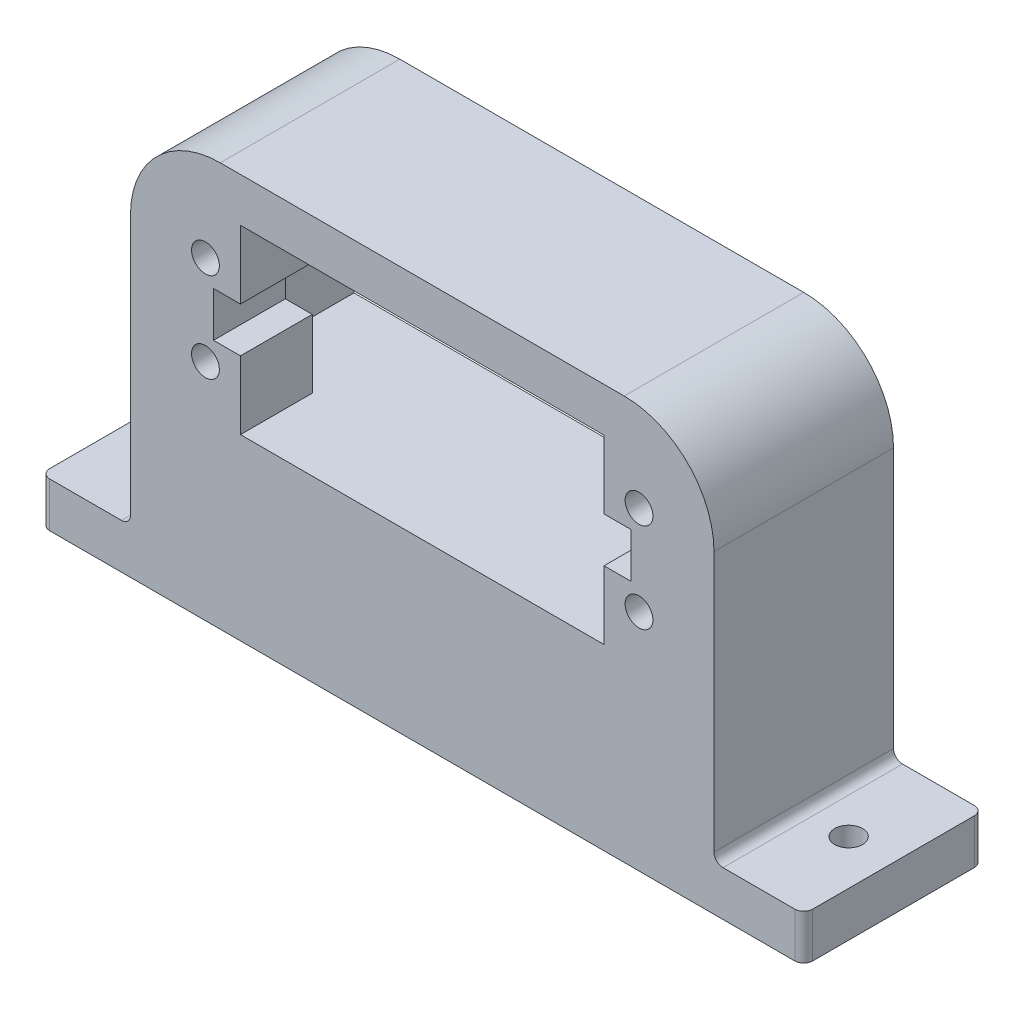
SolidWorks part; units mm, degrees
ref_plane "Front Plane" through (0, 0, 0) normal (0, 0, 1) x (1, 0, 0)
ref_plane "Top Plane" through (0, 0, 0) normal (0, 1, 0) x (1, 0, 0)
ref_plane "Right Plane" through (0, 0, 0) normal (1, 0, 0) x (0, 0, -1)
sketch "Sketch1" plane through (0, 0, 0) normal (0, 0, 1) x (1, 0, 0)
  line L0 (-42.5, 0) -> (42.5, 0)
  line L1 (32.5, 5) -> (32.5, 35)
  line L2 (22.5, 45) -> (-22.5, 45)
  line L3 (-32.5, 35) -> (-32.5, 5)
  line L4 (-42.5, 0) -> (-42.5, 5)
  line L5 (-42.5, 5) -> (-32.5, 5)
  line L7 (42.5, 0) -> (42.5, 5)
  line L8 (42.5, 5) -> (32.5, 5)
  arc A1 (32.5, 35) -> (22.5, 45) centre (22.5, 35) ccw
  arc A2 (-22.5, 45) -> (-32.5, 35) centre (-22.5, 35) ccw
  dimension "D1" = 10
  dimension "D2" = 45
  dimension "D3" = 65
  dimension "D4" = 10
  dimension "D5" = 5
extrude "Boss-Extrude1" add sketch "Sketch1" along normal mid plane 20
sketch "Sketch3" plane through (0, 0, -10) normal (0, 0, -1) x (-1, 0, 0)
  line L0 (-24.15, 25) -> (-24.15, 35) construction
  line L1 (-27.6, 19.9) -> (27.6, 19.9)
  line L2 (-27.6, 19.9) -> (-27.6, 40.1)
  line L3 (-27.6, 40.1) -> (27.6, 40.1)
  line L4 (27.6, 19.9) -> (27.6, 40.1)
  line L5 (-27.6, 19.9) -> (27.6, 40.1) construction
  line L6 (-27.6, 40.1) -> (27.6, 19.9) construction
  line L7 (20.25, 19.9) -> (-20.25, 19.9)
  line L8 (20.25, 19.9) -> (20.25, 40.1)
  line L9 (20.25, 40.1) -> (-20.25, 40.1)
  line L10 (-20.25, 19.9) -> (-20.25, 40.1)
  line L11 (20.25, 19.9) -> (-20.25, 40.1) construction
  line L12 (20.25, 40.1) -> (-20.25, 19.9) construction
  line L13 (24.15, 25) -> (24.15, 35) construction
  line L14 (-24.15, 30) -> (24.15, 30) construction
  line L15 (-20.25, 27.5) -> (-23.25, 27.5)
  line L16 (-23.25, 27.5) -> (-23.25, 32.5)
  line L17 (-23.25, 32.5) -> (-20.25, 32.5)
  line L19 (20.25, 32.5) -> (23.25, 32.5)
  line L20 (23.25, 32.5) -> (23.25, 27.5)
  line L21 (23.25, 27.5) -> (20.25, 27.5)
  circle A0 centre (-24.15, 25) radius 1.55
  circle A1 centre (24.15, 25) radius 1.55
  circle A2 centre (-24.15, 35) radius 1.55
  circle A3 centre (24.15, 35) radius 1.55
  point P0 (0, 30)
  point P7 (0, 30)
  point P22 (0, 30)
  point P27 (-23.25, 30)
  point P28 (-21.75, 32.5)
  point P34 (23.25, 30)
  dimension "D5" = 3.1
  dimension "D1" = 30
  dimension "D2" = 55.2
  dimension "D3" = 20.2
  dimension "D4" = 40.5
  dimension "D6" = 48.3
  dimension "D7" = 10
  dimension "D8" = 5
  dimension "D9" = 3
extrude "Cut-Extrude1" cut sketch "Sketch3" against normal blind 12 contours L8 L1 L4 L3 | L1 L10 L3 L2 region at (24.1719, 30, -10) region at (-24.1719, 30, -10)
extrude "Cut-Extrude3" cut sketch "Sketch3<3>" against normal through all contours L10 L1 L8 L3 | A0 | A3 | L17 L16 L15 L10 | L21 L20 L19 L8 | A2 | A1 region at (0, 30, -10) region at (21.75, 30, -10) region at (-21.75, 30, -10) region at (24.15, 25, -10) region at (-24.15, 35, -10)
sketch "Sketch3<3>" plane through (0, 0, -10) normal (0, 0, -1) x (-1, 0, 0) same geometry as "Sketch3"
sketch "Sketch5" plane through (0, 5, 0) normal (0, 1, 0) x (1, 0, 0)
  line L0 (42.5, 10) -> (32.5, 10) construction
  line L1 (37.5, -10) -> (37.5, 10) construction
  line L2 (42.5, -10) -> (32.5, -10) construction
  circle A0 centre (37.5, 0) radius 1.55
  point P4 (37.5, 0)
  dimension "D1" = 3.1
extrude "Cut-Extrude4" cut sketch "Sketch5" against normal through all
mirror "Mirror3" about plane through (0, 0, 0) normal (1, 0, 0) of "Cut-Extrude4"
fillet "Fillet1" radius 1 6 edges at (42.5, 2.5, 10) (42.5, 2.5, -10) (32.5, 5, 0) (-42.5, 2.5, 10) (-42.5, 2.5, -10) (-32.5, 5, 0)
